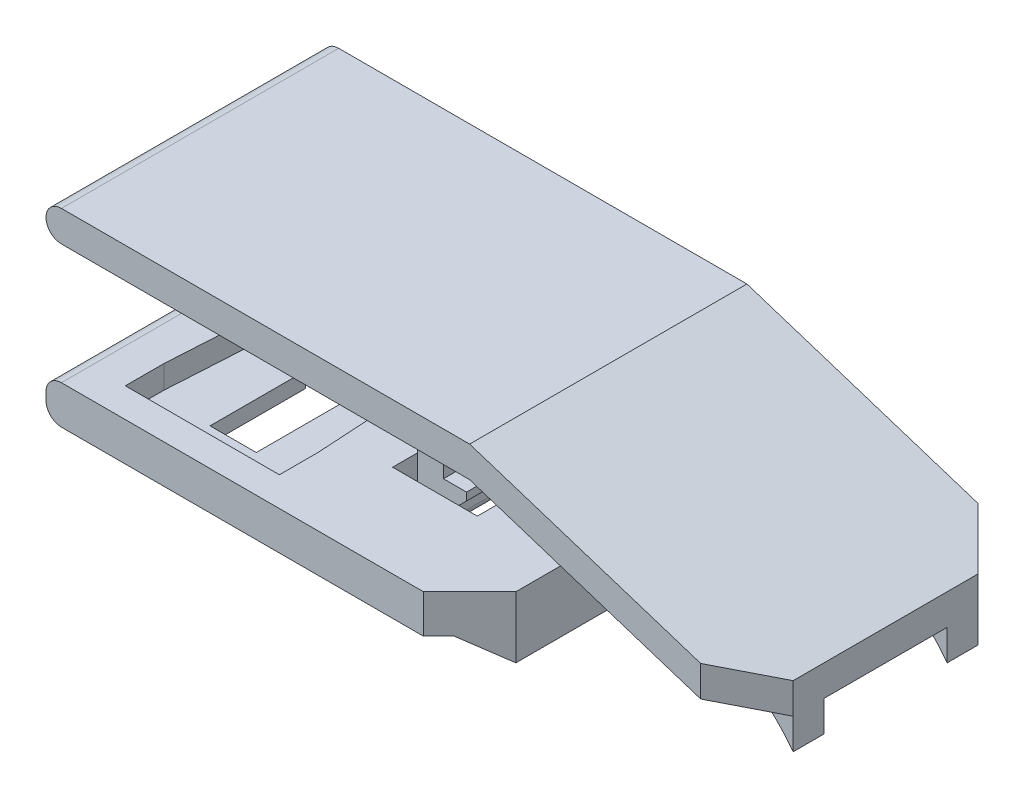
SolidWorks part; units mm, degrees
ref_plane "Front Plane" through (0, 0, 0) normal (0, 0, 1) x (1, 0, 0)
ref_plane "Top Plane" through (0, 0, 0) normal (0, 1, 0) x (1, 0, 0)
ref_plane "Right Plane" through (0, 0, 0) normal (1, 0, 0) x (0, 0, -1)
sketch "Sketch1" plane through (0, 0, 0) normal (0, 0, 1) x (1, 0, 0)
  line L0 (0, 0) -> (0, 4) construction
  line L1 (0, 0) -> (-18, 0) construction
  line L2 (0, 4) -> (-18, 9.8)
  line L3 (-18, 9.8) -> (-45.5, 9.8)
  line L4 (-18, 0) -> (-45.5, 0)
  line L5 (-18, 7.8) -> (-45.5, 7.8)
  line L6 (-45.5, 7.8) -> (-45.5, 9.8)
  line L8 (-45.5, -2.5) -> (-20, -2.5)
  line L9 (-20, -2.5) -> (-18, -4)
  line L10 (-18, 0) -> (-18, 3.5) construction
  line L11 (-18, 3.5) -> (-18, 7.8) construction
  line L12 (-18, 0) -> (-18, -4)
  line L17 (-45.5, 0) -> (-45.5, -2.5)
  line L21 (-18, 7.8) -> (0, 2)
  line L22 (0, 2) -> (0, 4)
  dimension "D5" = 27.5
  dimension "D2" = 18
  dimension "D3" = 3.5
  dimension "D4" = 2.5
  dimension "D6" = 27.5
  dimension "D7" = 4.3
  dimension "D8" = 2
  dimension "D9" = 2
  dimension "D10" = 2
  dimension "D11" = 162.14
  dimension "D16" = 1.5
other "AlignGroup1"
extrude "Boss-Extrude1" add sketch "Sketch1" along normal blind 18
sketch "Sketch2" plane through (0, -2.5, 0) normal (0, -1, 0) x (1, 0, 0)
  line L0 (-20, 18) -> (-20, 0) construction
  line L1 (-29, 12) -> (-23.5, 12)
  line L2 (-29, 12) -> (-29, 6)
  line L3 (-29, 6) -> (-23.5, 6)
  line L4 (-23.5, 12) -> (-23.5, 6)
  line L7 (-20, 9) -> (-45.5, 9) construction
  line L8 (-45.5, 18) -> (-45.5, 0) construction
  point P9 (-23.5, 9)
  dimension "D1" = 3.5
  dimension "D2" = 5.5
  dimension "D3" = 6
extrude "Cut-Extrude1" cut sketch "Sketch2" against normal blind 3
sketch "Sketch3" plane through (0, 0, 6) normal (0, 0, 1) x (1, 0, 0)
  line L0 (-23.5, 0) -> (-25.5, -2)
  line L1 (-25.5, -2) -> (-25.5, -2.5)
  line L2 (-18, -4) -> (-18, 0) construction
  line L3 (-25.5, -2.5) -> (-23.5, -2.5)
  line L4 (-23.5, -2.5) -> (-23.5, 0)
  line L5 (-45.5, -2.5) -> (-20, -2.5) construction
  line L6 (-18, 0) -> (-45.5, 0) construction
  point P2 (-18, -2)
  dimension "D1" = 0.5
  dimension "D2" = 2
  dimension "D3" = 5.5
extrude "Boss-Extrude2" add sketch "Sketch3" along normal up to surface (6 mm away) up to face at (-26.25, -1.25, 12)
sketch "Sketch4" plane through (0, 0, 18) normal (0, 0, 1) x (1, 0, 0)
  line L0 (-26.7, -2) -> (-24.7, 0)
  line L2 (-24.7, 0) -> (-24.7, 0.5)
  line L3 (-24.7, 0.5) -> (-26.2, 0.5)
  line L4 (-26.2, 0.5) -> (-26.2, 1.5)
  line L6 (-26.7, -2) -> (-26.7, -3)
  line L7 (-26.7, -3) -> (-27.9, -3)
  line L8 (-27.9, -3) -> (-27.9, 1.5)
  line L9 (-45.5, 7.8) -> (-18, 7.8) construction
  line L10 (-25.5, -2) -> (-25.5, -2.5) construction
  line L11 (-26.2, 1.5) -> (-29.0621, 4.3621) construction
  line L12 (-26.2, 1.5) -> (-19.9, 7.8)
  line L13 (-27.4021, 2.7021) -> (-22.3042, 7.8)
  line L14 (-18, 0) -> (-45.5, 0) construction
  line L16 (-22.3042, 7.8) -> (-19.9, 7.8)
  arc A0 (-27.4021, 2.7021) -> (-27.9, 1.5) centre (-26.2, 1.5) ccw
  dimension "D1" = 1.5
  dimension "D2" = 1.2
  dimension "D3" = 45
  dimension "D4" = 0.5
  dimension "D5" = 1.2
  dimension "D6" = 1
  dimension "D7" = 2
  dimension "D8" = 1
  dimension "D9" = 45
extrude "Boss-Extrude3" add sketch "Sketch4" against normal mid plane 5 from offset 9 offset against normal yes
fillet "Fillet7" radius 1 1 edges at (-45.5, 0, 9)
fillet "Fillet8" radius 1 1 edges at (-45.5, 7.8, 9)
fillet "Fillet10" radius 1 1 edges at (-45.5, 9.8, 9)
fillet "Fillet11" radius 1 1 edges at (-45.5, -2.5, 9)
sketch "Sketch5" plane through (0, 0, 18) normal (0, 0, 1) x (1, 0, 0)
  line L0 (0, 2) -> (0, 0)
  line L1 (-18, 7.8) -> (0, 2) construction
  line L2 (-5.0026, 3.612) -> (0, 2)
  arc A0 (-5.0026, 3.612) -> (0, 0) centre (-8.0695, -5.9061) cw
  dimension "D1" = 10
extrude "Boss-Extrude4" add sketch "Sketch5" against normal blind 2 from offset 3 offset against normal yes
extrude "Boss-Extrude5" add sketch "Sketch5<2>" along normal blind 2 from offset 15 offset against normal yes
sketch "Sketch5<2>" plane through (0, 0, 18) normal (0, 0, 1) x (1, 0, 0) same geometry as "Sketch5"
fillet "Fillet12" radius 0.5 2 edges at (-26.7, -3, 9) (-27.9, -3, 9)
fillet "Fillet13" radius 0.5 1 edges at (-26.2, 1.5, 9)
sketch "Sketch6" plane through (0, 0, 0) normal (0, -1, 0) x (1, 0, 0)
  line L0 (-42.5, 16.1) -> (-42.25, 16.1) construction
  line L1 (-32, 1.9) -> (-32.8, 1.9) construction
  line L2 (-42.5, 16.1) -> (-42.5, 1.9) construction
  line L3 (-32, 16.1) -> (-32, 1.9) construction
  line L4 (-44.5, 0) -> (-44.5, 18) construction
  line L5 (-32.8, 1.9) -> (-41.7, 1.9)
  line L6 (-41.7, 1.9) -> (-42.5, 1.9) construction
  line L7 (-42.25, 13.6045) -> (-42.25, 16.1)
  line L8 (-42.25, 13.6045) -> (-41.7, 4.3955)
  line L9 (-41.7, 4.3955) -> (-41.7, 1.9)
  line L10 (-32.8, 1.9) -> (-32.8, 4.3955)
  line L11 (-42.5, 16.1) -> (-42.5, 18) construction
  line L12 (-44.5, 18) -> (-20, 18) construction
  line L13 (-42.5, 1.9) -> (-42.5, 0) construction
  line L14 (-44.5, 0) -> (-20, 0) construction
  line L15 (-32.8, 4.3955) -> (-32.25, 13.6045)
  line L16 (-32.25, 13.6045) -> (-32.25, 16.1)
  line L17 (-42.25, 16.1) -> (-32.25, 16.1)
  line L18 (-32.25, 16.1) -> (-32, 16.1) construction
  dimension "D1" = 10.5
  dimension "D2" = 2
  dimension "D3" = 14.2
  dimension "D4" = 8.9
  dimension "D5" = 2.4955
  dimension "D6" = 10
extrude "Cut-Extrude2" cut sketch "Sketch6" along normal blind 1.5 and the other way blind 9
sketch "Sketch7" plane through (0, 9.8, 0) normal (0, 1, 0) x (1, 0, 0)
  line L0 (0, -3) -> (-3, 0)
  line L1 (0, -18) -> (0, 0) construction
  line L2 (0, 0) -> (-18, 0) construction
  line L3 (-3, 0) -> (-45.5, 0)
  line L4 (-45.5, -18) -> (-3, -18)
  line L9 (-45.5, 0) -> (-45.5, -18)
  line L15 (0, -18) -> (-18, -18) construction
  line L16 (-3, -18) -> (0, -15)
  line L17 (0, -3) -> (2, -3)
  line L18 (2, -3) -> (2, 2)
  line L19 (2, 2) -> (-48, 2)
  line L20 (-48, 2) -> (-48, -20)
  line L21 (-48, -20) -> (2, -20)
  line L22 (2, -20) -> (2, -15)
  line L23 (2, -15) -> (0, -15)
  line L24 (-45.5, -18) -> (-45.5, -20) construction
  line L25 (-45.5, 0) -> (-45.5, 2) construction
  dimension "D1" = 2.5
  dimension "D2" = 135
  dimension "D3" = 2
  dimension "D5" = 2
extrude "Cut-Extrude3" cut sketch "Sketch7" against normal through all
sketch "Sketch8" plane through (0, -2.5, 0) normal (0, -1, 0) x (1, 0, 0)
  line L0 (-18, 15) -> (-16, 15)
  line L1 (-21, 18) -> (-18, 15)
  line L2 (-44.5, 18) -> (-20, 18) construction
  line L3 (-45.5, 18) -> (-21, 18)
  line L4 (-18, 3) -> (-21, 0)
  line L5 (-44.5, 0) -> (-20, 0) construction
  line L6 (-21, 0) -> (-45.5, 0)
  line L7 (-45.5, 0) -> (-45.5, 18)
  line L8 (-45.5, 0) -> (-45.5, 18) construction
  line L9 (-16, 15) -> (-16, 20)
  line L10 (-16, 20) -> (-47.5, 20)
  line L11 (-47.5, 20) -> (-47.5, -2)
  line L12 (-47.5, -2) -> (-16, -2)
  line L13 (-16, -2) -> (-16, 3)
  line L14 (-16, 3) -> (-18, 3)
  line L15 (-18, 18) -> (-18, 0) construction
  dimension "D1" = 135
  dimension "D2" = 2
  dimension "D3" = 2
  dimension "D4" = 2
  dimension "D5" = 12
  dimension "D6" = 2
extrude "Cut-Extrude9" cut sketch "Sketch8" against normal up to next (9.9778 mm away) and the other way through all
sketch "Sketch9" plane through (0, -1.5, 0) normal (0, -1, 0) x (1, 0, 0)
  line L0 (-38.75, 14.1) -> (-35.75, 14.1)
  line L1 (-35.75, 14.1) -> (-35.75, 7.9)
  line L2 (-35.75, 7.9) -> (-33.25, 7.9)
  line L3 (-33.25, 7.9) -> (-37.25, 3.9)
  line L4 (-37.25, 3.9) -> (-41.25, 7.9)
  line L5 (-41.25, 7.9) -> (-38.75, 7.9)
  line L6 (-38.75, 7.9) -> (-38.75, 14.1)
  line L7 (-37.25, 3.9) -> (-37.25, 1.9) construction
  line L8 (-41.7, 1.9) -> (-32.8, 1.9) construction
  line L10 (-41.25, 7.9) -> (-41.9093, 7.9) construction
  line L11 (-42.25, 13.6045) -> (-41.7, 4.3955) construction
  line L12 (-33.25, 7.9) -> (-32.5907, 7.9) construction
  line L13 (-32.8, 4.3955) -> (-32.25, 13.6045) construction
  line L14 (-37.25, 14.1) -> (-37.25, 16.1) construction
  line L15 (-32.25, 16.1) -> (-42.25, 16.1) construction
  dimension "D1" = 3
  dimension "D2" = 4
  dimension "D3" = 2
extrude "Cut-Extrude10" cut sketch "Sketch9" along normal up to next (1 mm away)
sketch "Sketch11" plane through (0, 0, 0) normal (0, 0, 1) x (1, 0, 0)
  line L0 (-16, 0) -> (-9, 0)
  line L1 (-21, 0) -> (-44.5, 0) construction
  line L3 (-16, 0) -> (-18, 0) construction
  arc A0 (-9, 0) -> (-16, 0) centre (-12.5, 0) ccw
  dimension "D1" = 3.5
  dimension "D2" = 2
extrude "Boss-Extrude8" add sketch "Sketch11" along normal blind 4 from offset 7 separate body
